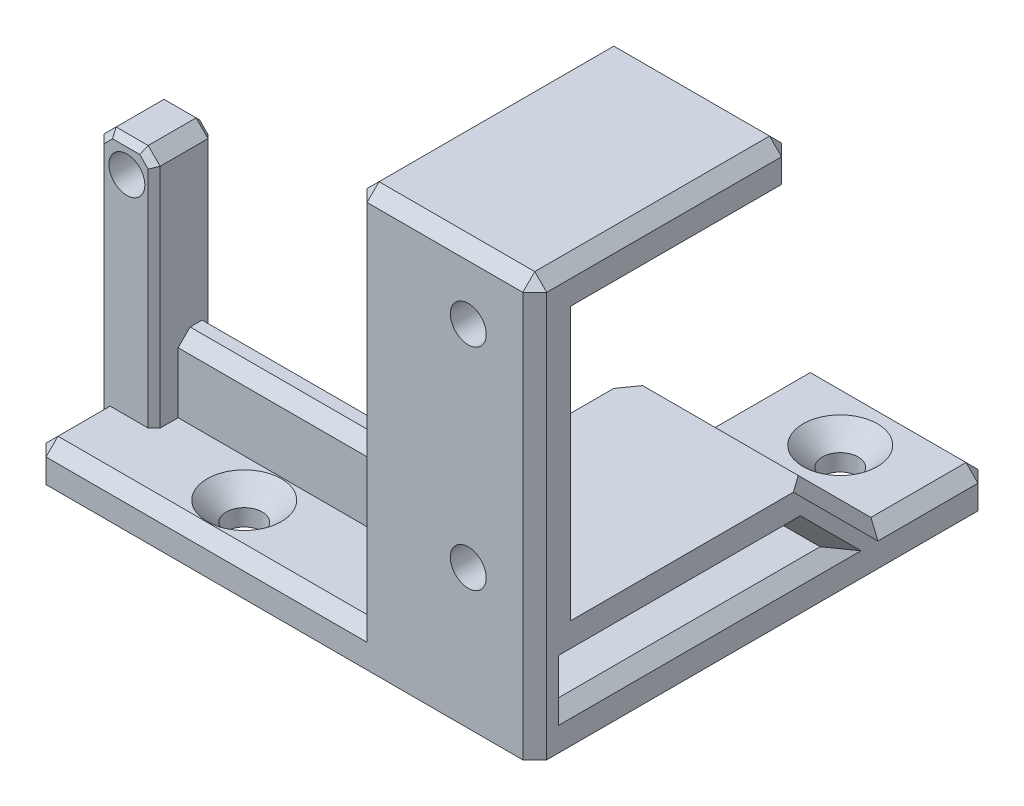
SolidWorks part; units mm, degrees
ref_plane "Plano frontal" through (0, 0, 0) normal (0, 0, 1) x (1, 0, 0)
ref_plane "Plano superior" through (0, 0, 0) normal (0, 1, 0) x (1, 0, 0)
ref_plane "Plano direito" through (0, 0, 0) normal (1, 0, 0) x (0, 0, -1)
sketch "Esboço1" plane through (0, 0, 0) normal (0, 0, 1) x (1, 0, 0)
  line L3 (-9.6018, -16.4271) -> (-9.6018, 15.2529) construction
  line L4 (-9.6018, 15.2529) -> (5.3982, 15.2529) construction
  line L5 (5.3982, 15.2529) -> (5.3982, -16.4271) construction
  line L6 (5.3982, -16.4271) -> (-9.6018, -16.4271) construction
  line L7 (-9.6018, -7.2471) -> (5.3982, -7.2471) construction
  line L8 (-31.6018, 1.5029) -> (-36.1018, 1.5029) construction
  line L9 (-36.4018, 1.8029) -> (-36.4018, 6.2029) construction
  line L10 (-36.1018, 6.5029) -> (-31.6018, 6.5029) construction
  line L11 (16.5982, -3.1831) -> (5.3982, -3.1831) construction
  line L12 (16.5982, 11.1889) -> (16.5982, -3.1831) construction
  line L13 (5.3982, 11.1889) -> (16.5982, 11.1889) construction
  line L14 (5.0982, -7.2471) -> (-27.6018, -7.2471) construction
  line L15 (-31.6018, -3.2471) -> (-31.6018, 11.2529) construction
  line L16 (-27.6018, 15.2529) -> (5.0982, 15.2529) construction
  line L17 (10.0982, -1.6971) -> (18.8619, -1.6971) construction
  line L18 (9.0982, 8.7029) -> (9.0982, -0.6971) construction
  line L19 (18.8619, 9.7029) -> (10.0982, 9.7029) construction
  line L20 (40.6534, -16.4271) -> (-43.0018, -16.4271) construction
  line L21 (-18.1518, 5.9695) -> (-18.1518, 2.0363) construction
  line L22 (-21.8518, 2.0363) -> (-21.8518, 5.9695) construction
  circle A0 centre (-0.1518, 12.8029) radius 1.5 construction
  circle A1 centre (-0.1518, -4.7971) radius 1.5 construction
  circle A2 centre (-34.0018, 4.0029) radius 1.5 construction
  arc A3 (-36.4018, 1.8029) -> (-36.1018, 1.5029) centre (-36.1018, 1.8029) ccw construction
  arc A4 (-36.1018, 6.5029) -> (-36.4018, 6.2029) centre (-36.1018, 6.2029) ccw construction
  arc A5 (-31.6018, -3.2471) -> (-27.6018, -7.2471) centre (-27.6018, -3.2471) ccw construction
  arc A6 (-27.6018, 15.2529) -> (-31.6018, 11.2529) centre (-27.6018, 11.2529) ccw construction
  arc A7 (9.0982, -0.6971) -> (10.0982, -1.6971) centre (10.0982, -0.6971) ccw construction
  arc A8 (10.0982, 9.7029) -> (9.0982, 8.7029) centre (10.0982, 8.7029) ccw construction
  circle A9 centre (-20.0018, 4.0029) radius 0.975 construction
  arc A10 (-18.1518, 2.0363) -> (-18.1518, 5.9695) centre (-20.0018, 4.0029) ccw construction
  arc A11 (-21.8518, 2.0363) -> (-18.1518, 2.0363) centre (-20.0018, 4.0029) ccw construction
  circle A12 centre (-20.0018, 4.0029) radius 3.05 construction
  arc A13 (-21.8518, 5.9695) -> (-21.8518, 2.0363) centre (-20.0018, 4.0029) ccw construction
  arc A14 (-18.1518, 5.9695) -> (-21.8518, 5.9695) centre (-20.0018, 4.0029) ccw construction
  circle A15 centre (-20.0018, 4.0029) radius 8.9 construction
  dimension "D1" = 15
sketch "Esboço3" plane through (0, 0, 0) normal (0, 0, 1) x (1, 0, 0)
  line L0 (-9.6018, -16.4271) -> (-9.6018, 18.3729)
  line L1 (-9.6018, 18.3729) -> (5.3982, 18.3729)
  line L3 (5.3982, -16.4271) -> (-9.6018, -16.4271)
  line L4 (-9.6018, 15.2529) -> (5.3982, 15.2529) construction
  line L5 (5.3982, 18.3729) -> (5.3982, -16.4271)
  point P12 (5.3982, -16.4271)
  point P13 (13.649, 18.3729)
  dimension "D1" = 3.12
extrude "Ressalto-extrusão1" add sketch "Esboço3" along normal blind 3
sketch "Esboço5" plane through (0, 0, 0) normal (0, 0, -1) x (-1, 0, 0)
  line L0 (9.6018, 18.3729) -> (9.6018, -16.4271) construction
  line L1 (-5.3982, 18.3729) -> (9.6018, 18.3729)
  line L2 (-5.3982, 18.3729) -> (-5.3982, 15.3729)
  line L3 (-5.3982, 15.3729) -> (9.6018, 15.3729)
  line L4 (9.6018, 18.3729) -> (9.6018, 15.3729)
  line L12 (9.6018, 15.2529) -> (-5.3982, 15.2529) construction
  line M6 (9.6018, -16.4271) -> (9.6018, 18.3729)
  line M7 (9.6018, 18.3729) -> (-5.3982, 18.3729)
  line M8 (-5.3982, 18.3729) -> (-5.3982, -16.4271)
  dimension "D2" = 0.12
  dimension "D4" = 3
extrude "Ressalto-extrusão2" add sketch "Esboço5" along normal blind 18.6 contours L3 M8 M6 M7
sketch "Esboço6" plane through (0, 0, 0) normal (0, 0, -1) x (-1, 0, 0)
  line L0 (9.6018, -16.4271) -> (9.6018, 15.2529) construction
  line L1 (-5.3982, -16.4271) -> (9.6018, -16.4271)
  line L2 (-5.3982, -16.4271) -> (-5.3982, -13.4271)
  line L3 (-5.3982, -13.4271) -> (9.6018, -13.4271)
  line L4 (9.6018, -16.4271) -> (9.6018, -13.4271)
  dimension "D1" = 3
extrude "Ressalto-extrusão3" add sketch "Esboço6" along normal blind 35
sketch "Esboço8" plane through (0, 0, 0) normal (0, 0, -1) x (-1, 0, 0)
  circle A0 centre (0.1518, 12.8029) radius 1.5
  circle A1 centre (0.1518, -4.7971) radius 1.5
  dimension "D1" = 3
  dimension "D2" = 3
extrude "Corte-extrusão1" cut sketch "Esboço8" against normal blind 15
sketch "Esboço10" plane through (0, -13.4271, 0) normal (0, 1, 0) x (1, 0, 0)
  line L0 (-9.6018, 30) -> (-2.1018, 30) construction
  line L3 (-2.1018, 30) -> (-2.1018, 35) construction
  line L4 (-9.6018, 35) -> (-9.6018, 0) construction
  line L6 (-2.1018, 30) -> (5.3982, 30) construction
  line L8 (-9.6018, 35) -> (5.3982, 35) construction
  line L9 (5.3982, 35) -> (5.3982, 0) construction
  circle A4 centre (-2.1018, 30) radius 1.5
  dimension "D1" = 3
  dimension "D3" = 5
extrude "Corte-extrusão3" cut sketch "Esboço10" against normal blind 15
chamfer "Chanfro2" distance 1.6 angle 45 1 edges at (-2.1018, -13.4271, -28.5)
sketch "Esboço11" plane through (5.3982, 0, 0) normal (1, 0, 0) x (0, 0, -1)
  line L0 (0, -7.3671) -> (20, -7.3671)
  line L2 (20, -7.3671) -> (26.06, -13.4271)
  line L9 (0, -10.3671) -> (18.7574, -10.3671)
  line L10 (18.7574, -10.3671) -> (21.8174, -13.4271)
  line L11 (21.8174, -13.4271) -> (26.06, -13.4271)
  line L12 (0, -7.3671) -> (0, -10.3671)
  line L13 (0, -10.3671) -> (0, -13.4271) construction
  line L14 (0, -13.4271) -> (21.8174, -13.4271) construction
  line L15 (-3, -7.3671) -> (20, -7.3671) construction
  line L16 (-3, -7.3671) -> (-3, -16.4271) construction
  line L17 (-3, -16.4271) -> (29.06, -16.4271) construction
  line L18 (20, -7.3671) -> (29.06, -16.4271) construction
  dimension "D1" = 0.12
  dimension "D2" = 3
extrude "Ressalto-extrusão5" add sketch "Esboço11" against normal up to vertex (15 mm away) contours L0 L2 L11 L10 L9 L12
ref_plane "Plano1" through (0, 0, -7.35) normal (0, 0, 1) x (1, 0, 0)
sketch "Esboço14" plane through (0, 0, -7.35) normal (0, 0, 1) x (1, 0, 0)
  line L0 (-31.7218, 6.5029) -> (-31.7218, -7.3671)
  line L1 (40.6534, -16.4271) -> (-43.0018, -16.4271) construction
  line L2 (-31.6018, -3.2471) -> (-31.6018, 11.2529) construction
  line L3 (-31.7218, 6.5029) -> (-36.4018, 6.5029)
  line L4 (-36.4018, 6.5029) -> (-36.4018, -16.4271)
  line L5 (-36.4018, -16.4271) -> (-31.7218, -16.4271)
  line L6 (-36.4018, 1.8029) -> (-36.4018, 6.2029) construction
  line L7 (-36.1018, 6.5029) -> (-31.6018, 6.5029) construction
  line L8 (-31.7218, -16.4271) -> (-9.6018, -16.4271)
  line L9 (-9.6018, -16.4271) -> (-9.6018, -7.3671)
  line L10 (-9.6018, -16.4271) -> (-9.6018, 15.2529) construction
  line L11 (-9.6018, -7.3671) -> (-31.7218, -7.3671)
  line L12 (5.0982, -7.2471) -> (-27.6018, -7.2471) construction
  circle A1 centre (-34.0018, 4.0029) radius 1.5 construction
  circle A2 centre (-34.0018, 4.0029) radius 1.5
  dimension "D2" = 0.12
  dimension "D3" = 0
  dimension "D4" = 0
  dimension "D5" = 0.12
extrude "Ressalto-extrusão7" add sketch "Esboço14" along normal blind 3
sketch "Esboço16" plane through (-9.6018, 0, 0) normal (-1, 0, 0) x (0, 0, 1)
  line L12 (-4.35, -13.4271) -> (-4.35, -16.4271)
  line L13 (-4.35, -16.4271) -> (3, -16.4271)
  line L14 (3, -16.4271) -> (3, 18.3729)
  line L15 (3, 18.3729) -> (-18.6, 18.3729)
  line L16 (-18.6, 18.3729) -> (-18.6, 15.3729)
  line L17 (-18.6, 15.3729) -> (0, 15.3729)
  line L18 (0, 15.3729) -> (0, -7.3671)
  line L19 (0, -7.3671) -> (-4.35, -7.3671)
  line L20 (-4.35, -7.3671) -> (-4.35, -10.3671)
  line L21 (-4.35, -10.3671) -> (0, -10.3671)
  line L22 (0, -10.3671) -> (0, -13.4271)
  line L23 (0, -13.4271) -> (-4.35, -13.4271)
  line L24 (-4.35, -13.4271) -> (-4.35, -16.4271)
  line L25 (-4.35, -16.4271) -> (3, -16.4271)
  line L26 (3, -16.4271) -> (3, -13.4271)
  line L35 (3, -13.4271) -> (-4.35, -13.4271)
  line M13 (-4.35, -13.4271) -> (-4.35, -16.4271)
  line M14 (-4.35, -16.4271) -> (3, -16.4271)
  line M15 (3, -16.4271) -> (3, 18.3729)
  line M24 (0, -13.4271) -> (-4.35, -13.4271)
  dimension "D1" = 0
extrude "Ressalto-extrusão9" add sketch "Esboço16" along normal up to surface (26.8 mm away) contours L35 M15 M24 M13 M14 up to face at (-36.4018, -4.9621, -5.85)
chamfer "Chanfro6" distance 1 angle 45 2 edges at (-9.6018, -11.8971, -7.35) (-9.6018, -11.8971, -4.35)
chamfer "Chanfro7" distance 1 angle 45 1 edges at (-9.6018, -13.4271, -14.5837)
chamfer "Chanfro8" distance 1 angle 45 3 edges at (-9.6018, -13.4271, -7.35) (-10.1018, -13.4271, -6.85) (-9.1018, -13.9271, -7.35)
sketch "Esboço19" plane through (0, 0, -4.35) normal (0, 0, 1) x (1, 0, 0)
  line L9 (-36.4018, -13.4271) -> (-10.6018, -13.4271)
  line L10 (-10.6018, -13.4271) -> (-10.6018, -10.3671)
  line L11 (-10.6018, -10.3671) -> (-9.6018, -10.3671)
  line L13 (-9.6018, -10.3671) -> (-9.6018, -7.3671)
  line L14 (-9.6018, -7.3671) -> (-31.7218, -7.3671)
  line L15 (-31.7218, -7.3671) -> (-31.7218, 6.5029)
  line L16 (-31.7218, 6.5029) -> (-36.4018, 6.5029)
  line L17 (-36.4018, 6.5029) -> (-36.4018, -13.4271)
  line L18 (-36.4018, -13.4271) -> (-31.7218, -13.4271)
  line L24 (-31.7218, -13.4271) -> (-31.7218, 6.5029)
  line L25 (-31.7218, 6.5029) -> (-36.4018, 6.5029)
  line L26 (-36.4018, 6.5029) -> (-36.4018, -13.4271)
  circle A0 centre (-34.0018, 4.0029) radius 1.5 construction
  circle A1 centre (-34.0018, 4.0029) radius 1.5
  dimension "D1" = 0
extrude "Ressalto-extrusão10" add sketch "Esboço19" along normal blind 2
sketch "Esboço17" plane through (0, -13.4271, 0) normal (0, 1, 0) x (1, 0, 0)
  line L0 (-23.0018, 1.15) -> (-23.0018, 4.35) construction
  line L1 (-9.6018, 4.35) -> (-31.7218, 4.35) construction
  circle A1 centre (-23.0018, 1.15) radius 1.5
  dimension "D2" = 3.2
  dimension "D1" = 3
extrude "Corte-extrusão4" cut sketch "Esboço17" against normal blind 7
chamfer "Chanfro4" distance 1 angle 45 30 edges at (-23.0018, -13.4271, 3) (-36.4018, -14.9271, 3) (-2.1018, 18.3729, 3) (-9.1018, -13.9271, -22.3174) (-9.6018, 2.4729, 3) (5.3982, 16.8729, -18.6) (-9.6018, 16.8729, -18.6) (-2.1018, 18.3729, -18.6) (-36.4018, -13.4271, 0.325) (5.3982, -11.8971, 0) (5.3982, -13.4271, -30.53) (5.3982, -14.9271, -35) (-9.6018, -14.9271, -35) (-2.1018, -13.4271, -35) (5.3982, -13.4271, -10.9087) (-9.6018, -11.8971, 0) (5.3982, -10.3971, -23.03) (-9.6018, -12.3971, -20.7874) (-9.6018, -10.3671, -2.175) (-9.6018, -10.3971, -23.03) (5.3982, -10.3671, -9.3787) (5.3982, -11.8971, -20.2874) (-9.6018, 18.3729, -7.8) (5.3982, 18.3729, -7.8) (-9.6018, -10.3671, -13.0537) (5.3982, 0.9729, 3) (-20.6618, -7.3671, -4.35) (-20.6618, -7.3671, -7.35) (-31.7218, 6.5029, -4.85) (-36.4018, 6.5029, -4.85)
chamfer "Chanfro10" distance 1.6 angle 45 1 edges at (-23.0018, -13.4271, 0.35)
chamfer "Chanfro11" distance 0.5 angle 45 10 edges at (-36.4018, -5.4621, -7.35) (-31.7218, -1.4321, -7.35) (-32.2218, 6.0029, -7.35) (-35.9018, 6.0029, -7.35) (-34.0618, 6.5029, -7.35) (-31.7218, -3.9621, -2.35) (-32.2218, 6.0029, -2.35) (-36.4018, -4.4621, -2.35) (-35.9018, 6.0029, -2.35) (-34.0618, 6.5029, -2.35)
